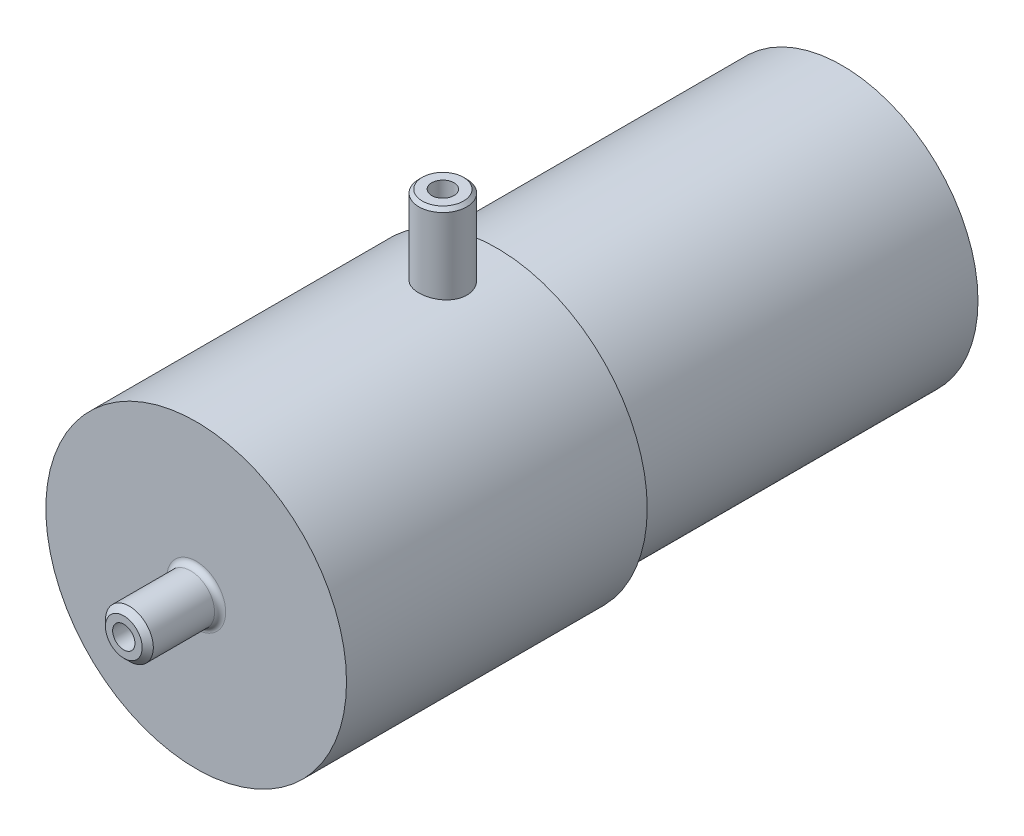
SolidWorks part; units mm, degrees
ref_plane "Alzado" through (0, 0, 0) normal (0, 0, 1) x (1, 0, 0)
ref_plane "Planta" through (0, 0, 0) normal (0, 1, 0) x (1, 0, 0)
ref_plane "Vista lateral" through (0, 0, 0) normal (1, 0, 0) x (0, 0, -1)
sketch "Croquis1" plane through (0, 0, 0) normal (0, 0, 1) x (1, 0, 0)
  circle A0 centre (0, 0) radius 12.2
  dimension "D1" = 24.4
extrude "Saliente-Extruir1" add sketch "Croquis1" along normal blind 31
sketch "Croquis2" plane through (0, 0, 31) normal (0, 0, 1) x (1, 0, 0)
  circle A0 centre (0, 0) radius 13.5
  dimension "D1" = 27
extrude "Saliente-Extruir2" add sketch "Croquis2" along normal blind 27
sketch "Croquis3" plane through (0, 0, 58) normal (0, 0, 1) x (1, 0, 0)
  circle A0 centre (0, 0) radius 2.15
  circle A1 centre (0, 0) radius 1
  dimension "D1" = 4.3
  dimension "D2" = 2
extrude "Saliente-Extruir3" add sketch "Croquis3" along normal blind 6.5
chamfer "Chaflán2" distance 0.5 1 edges at (2.15, 0, 64.5)
fillet "Redondeo1" radius 0.5 1 edges at (2.15, 0, 58)
ref_plane "Plano1" through (0, 13.5, 0) normal (0, 1, 0) x (1, 0, 0)
sketch "Croquis5" plane through (0, 13.5, 0) normal (0, 1, 0) x (1, 0, 0)
  line L1 (-13.5, -38) -> (13.5, -38) construction
  line L2 (-13.5, -31) -> (-13.5, -58) construction
  line L3 (13.5, -58) -> (13.5, -31) construction
  line L4 (13.5, -31) -> (-13.5, -31) construction
  line L6 (0, -31) -> (0, -58) construction
  line L7 (-2.65, -58) -> (2.65, -58) construction
  circle A0 centre (0, -35.85) radius 2.15
  circle A1 centre (0, -35.85) radius 1
  dimension "D1" = 7
  dimension "D2" = 4.3
  dimension "D3" = 2
extrude "Saliente-Extruir4" add sketch "Croquis5" along normal blind 7 and the other way up to surface other way up to face at (13.5, 0, 58)
chamfer "Chaflán3" distance 0.3 angle 45 1 edges at (0, 20.5, 38)
sketch "Croquis6" plane through (0, 0, 0) normal (0, 0, -1) x (-1, 0, 0)
  circle A0 centre (0, 0) radius 3
  dimension "D1" = 6
extrude "Saliente-Extruir5" add sketch "Croquis6" along normal blind 2
fillet "Redondeo2" radius 1 1 edges at (-3, 0, -2)
